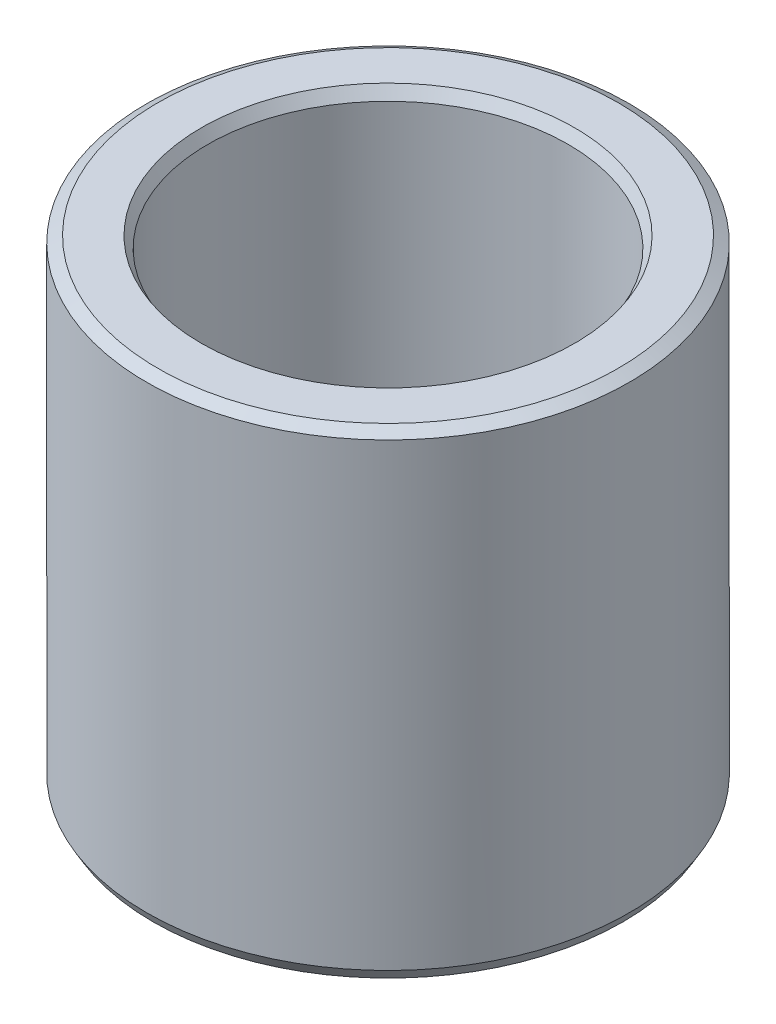
SolidWorks part; units mm, degrees
ref_plane "Front Plane" through (0, 0, 0) normal (0, 0, 1) x (1, 0, 0)
ref_plane "Top Plane" through (0, 0, 0) normal (0, 1, 0) x (1, 0, 0)
ref_plane "Right Plane" through (0, 0, 0) normal (1, 0, 0) x (0, 0, -1)
sketch "Sketch1" plane through (0, 0, 0) normal (0, 1, 0) x (1, 0, 0)
  circle A0 centre (0, 0) radius 57.5
  dimension "SLEEVE_OD" = 115
extrude "Boss-Extrude1" add sketch "Sketch1" along normal blind 113.6496
sketch "Sketch2" plane through (0, 0, 0) normal (0, 1, 0) x (1, 0, 0)
  circle A0 centre (0, 0) radius 42.9483
  dimension "BORE_D" = 85.8966
extrude "Cut-Extrude1" cut sketch "Sketch2" along normal through all
chamfer "Chamfer1" distance 1.5374 angle 60 4 edges at (0, 113.6496, 42.9483) (0, 0, 42.9483) (0, 0, 57.5) (0, 113.6496, 57.5) first distance on face at (0, 113.6496, 42.9483) first distance on face at (0, 0, 42.9483) first distance on face at (0, 113.6496, 57.5)
